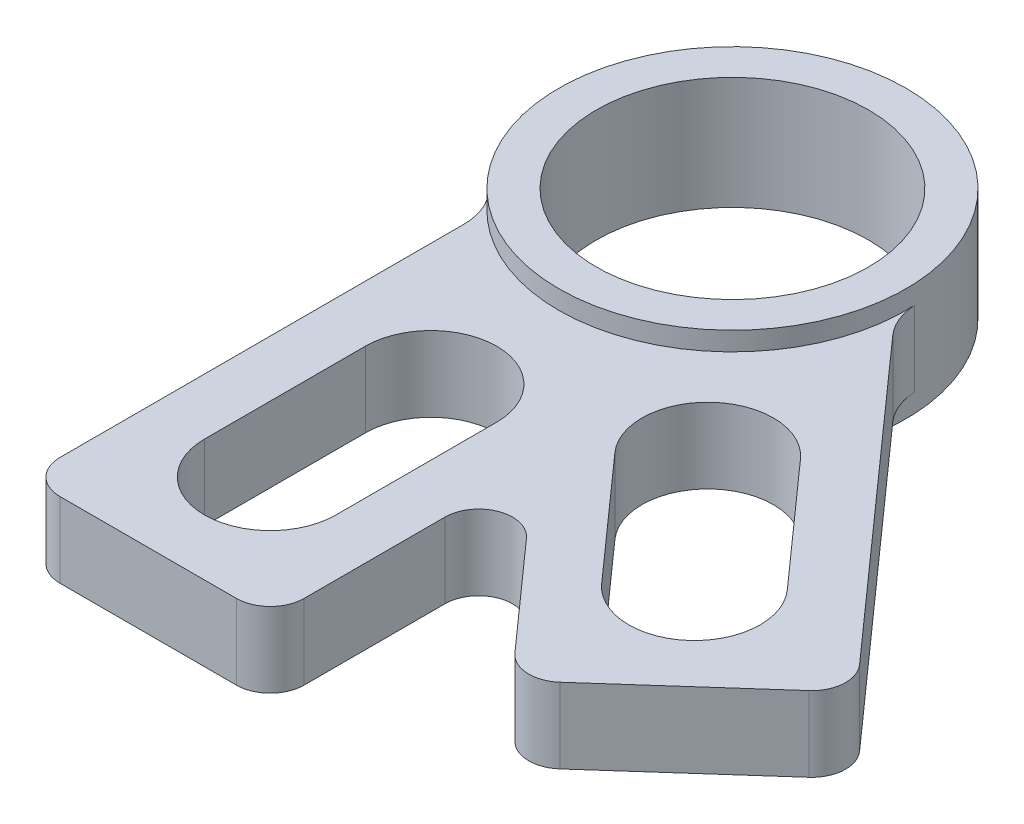
SolidWorks part; units mm, degrees
material "AISI 4130 Steel, annealed at 865C"
ref_plane "Front Plane" through (0, 0, 0) normal (0, 0, 1) x (1, 0, 0)
ref_plane "Top Plane" through (0, 0, 0) normal (0, 1, 0) x (1, 0, 0)
ref_plane "Right Plane" through (0, 0, 0) normal (1, 0, 0) x (0, 0, -1)
sketch "Sketch1" plane through (0, 0, 0) normal (0, 1, 0) x (1, 0, 0)
  line L0 (0, 0) -> (0, -49.3903) construction
  line L1 (0, 0) -> (32.8363, -36.8942) construction
  line L2 (0, -39.0716) -> (0, -25.4826) construction
  line L3 (-5.5562, -39.0716) -> (-5.5562, -25.4826)
  line L4 (5.5563, -39.0716) -> (5.5563, -25.4826)
  line L5 (25.976, -29.1862) -> (16.9416, -19.0353) construction
  line L6 (21.8256, -32.8801) -> (12.7911, -22.7292)
  line L7 (30.1265, -25.4922) -> (21.0921, -15.3413)
  line L8 (0, -49.3903) -> (0, -44.6278) construction
  line L9 (32.8363, -36.8942) -> (29.67, -33.3366) construction
  line L10 (-10.3187, -49.3903) -> (10.3188, -49.3903)
  line L11 (25.1282, -43.7544) -> (40.5443, -30.0339)
  line L12 (-10.3187, -49.3903) -> (-10.3187, -10.4432)
  line L13 (10.3188, -49.3903) -> (10.3188, -27.1148)
  line L14 (40.5443, -30.0339) -> (14.651, -0.9408)
  line L15 (25.1282, -43.7544) -> (10.3188, -27.1148)
  line L16 (196.1691, -220.4118) -> (13.8668, -15.5804) construction
  line L22 (0, 0) -> (10.3188, -27.1148) construction
  circle A0 centre (0, 0) radius 11.5062
  circle A1 centre (0, 0) radius 14.6812
  arc A2 (-5.5562, -39.0716) -> (5.5563, -39.0716) centre (0, -39.0716) ccw
  arc A3 (5.5563, -25.4826) -> (-5.5562, -25.4826) centre (0, -25.4826) ccw
  arc A4 (21.8256, -32.8801) -> (30.1265, -25.4922) centre (25.976, -29.1862) ccw
  arc A5 (21.0921, -15.3413) -> (12.7911, -22.7292) centre (16.9416, -19.0353) ccw
  point P8 (0, -32.2771)
  point P13 (21.4588, -24.1107)
  point P25 (0, -49.3903)
  point P27 (32.8363, -36.8942)
  dimension "D2" = 29.3624
  dimension "D3" = 4.7625
  dimension "D4" = 4.7625
  dimension "D5" = 13.589
  dimension "D6" = 49.3903
  dimension "D7" = 20.6375
extrude "Bearing_Insert_Extrude" add sketch "Sketch1" along normal mid plane 9.525 contours A1 A0 region at (-5.4988, 0, -13.1636)
extrude "Apex_Slot_Insert_Extrude" add sketch "Sketch1<4>" along normal mid plane 6.35 contours A1 L12 L10 L13 L15 L11 L14 A5 L7 A4 L6 A3 L4 A2 L3 region at (-9.6163, 0, 29.9168)
sketch "Sketch1<4>" plane through (0, 0, 0) normal (0, 1, 0) x (1, 0, 0) same geometry as "Sketch1"
fillet "Fillet1" radius 5.08 2 edges at (14.651, 0, 0.9408) (-10.3187, 0, 10.4432)
fillet "Fillet2" radius 2.8575 5 edges at (40.5443, 0, 30.0339) (25.1282, 0, 43.7544) (10.3188, 0, 27.1148) (10.3188, 0, 49.3903) (-10.3187, 0, 49.3903)
equation "\"Apex_thickness\"= .25"
equation "\"Bearing_diameter\"= 0.906in"
equation "\"A-arm_angle\"= 39.1893"
equation "\"D1@Sketch1\"=\"Bearing_diameter\""
equation "\"D1@Apex_Slot_Insert_Extrude\"=\"Apex_thickness\""
